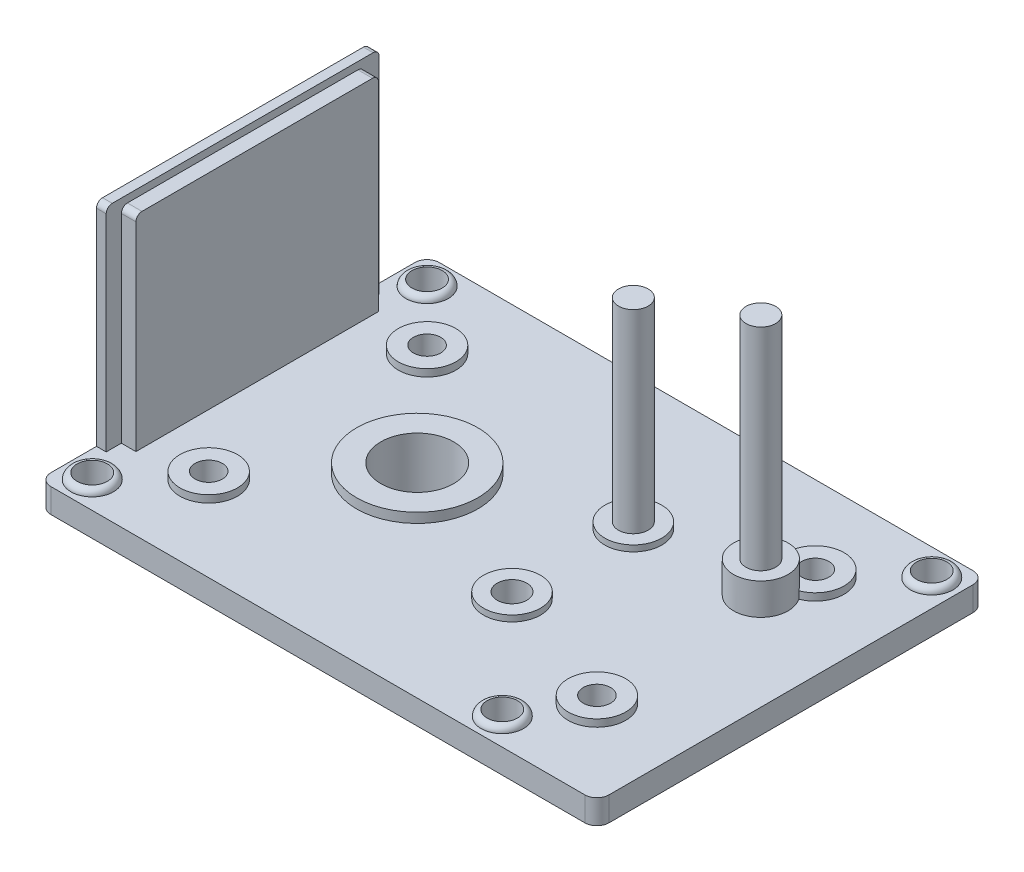
SolidWorks part; units mm, degrees
ref_plane "Front Plane" through (0, 0, 0) normal (0, 0, 1) x (1, 0, 0)
ref_plane "Top Plane" through (0, 0, 0) normal (0, 1, 0) x (1, 0, 0)
ref_plane "Right Plane" through (0, 0, 0) normal (1, 0, 0) x (0, 0, -1)
sketch "Sketch1" plane through (0, 0, 0) normal (0, 1, 0) x (1, 0, 0)
  line L0 (0, -55) -> (0, 55) construction
  line L1 (-23, 16) -> (23, 16)
  line L2 (-23, 16) -> (-23, -16)
  line L3 (-23, -16) -> (23, -16)
  line L4 (23, 16) -> (23, -16)
  line L5 (-55, 0) -> (55, 0) construction
  dimension "D1" = 46
  dimension "D2" = 23
  dimension "D3" = 32
  dimension "D4" = 16
extrude "Boss-Extrude1" add sketch "Sketch1" along normal blind 2
sketch "Sketch2" plane through (0, 2, 0) normal (0, 1, 0) x (1, 0, 0)
  line L0 (-23, -11.25) -> (-23, 11.25)
  line L1 (-1.1, 0) -> (1.1, 0) construction
  line L2 (-23, 16) -> (-23, -16) construction
  line L3 (-23, 11.25) -> (-22.2, 11.25)
  line L4 (-22.2, 11.25) -> (-22.2, 10)
  line L5 (-22.2, 10) -> (-21, 10)
  line L6 (-21, 10) -> (-21, -10)
  line L7 (-23, -11.25) -> (-22.2, -11.25)
  line L8 (-22.2, -11.25) -> (-22.2, -10)
  line L9 (-22.2, -10) -> (-21, -10)
  point P9 (-22.6, -11.25)
  point P11 (-23, 0)
  point P14 (-21, 0)
  dimension "D1" = 22.5
  dimension "D2" = 20
  dimension "D3" = 0.8
  dimension "D4" = 2
extrude "Boss-Extrude2" add sketch "Sketch2" along normal blind 17.5
sketch "Sketch3" plane through (0, 19.5, 0) normal (0, 1, 0) x (1, 0, 0)
  line L1 (-21, 10) -> (-22.2, 10)
  line L2 (-21, 10) -> (-21, -10)
  line L3 (-21, -10) -> (-22.2, -10)
  line L4 (-22.2, 10) -> (-22.2, -10)
extrude "Cut-Extrude1" cut sketch "Sketch3" against normal blind 0.6
fillet "Fillet1" radius 0.5 4 edges at (-22.6, 19.5, 11.25) (-21.6, 18.9, 10) (-22.6, 19.5, -11.25) (-21.6, 18.9, -10)
fillet "Fillet2" radius 1 4 edges at (-23, 1, -16) (23, 1, -16) (23, 1, 16) (-23, 1, 16)
sketch "Sketch4" plane through (0, 2, 0) normal (0, 1, 0) x (1, 0, 0)
  line L0 (23, -15) -> (23, 15) construction
  line L2 (22, 16) -> (-22, 16) construction
  line L5 (-23, 15) -> (-23, 11.25) construction
  line L7 (-1.1, 0) -> (1.1, 0) construction
  circle A1 centre (16, 9) radius 2.375
  circle A8 centre (-16, 9) radius 2.375
  circle A9 centre (16, -9) radius 2.375
  circle A10 centre (-16, -9) radius 2.375
  dimension "D1" = 7
  dimension "D3" = 4.75
  dimension "D4" = 4.75
  dimension "D2" = 7
  dimension "D5" = 7
  dimension "D6" = 7
extrude "Boss-Extrude3" add sketch "Sketch4" along normal blind 0.6
sketch "Sketch6" plane through (0, 2, 0) normal (0, 1, 0) x (1, 0, 0)
  line L0 (-1.1, 0) -> (1.1, 0) construction
  circle A3 centre (-16, 9) radius 1
  circle A7 centre (-16, 9) radius 2.375 construction
  circle A11 centre (-16, 9) radius 2.375 construction
  circle A12 centre (16, 9) radius 2.375
  circle A13 centre (16, 9) radius 2.375 construction
  circle A14 centre (16, 9) radius 1
  circle A15 centre (16, -9) radius 1
  circle A16 centre (-16, -9) radius 1
  dimension "D1" = 0
  dimension "D3" = 2
  dimension "D2" = 2
extrude "Boss-Extrude4" add sketch "Sketch6" along normal blind 0.75
hole_wizard "CSK for M6 Hex Socket Countersunk Cap Screw1" positions "Sketch11" profile "Sketch12" countersink size "M6" standard "ISO" end condition through all
sketch "Sketch11" plane through (0, 0, 0) normal (0, -1, 0) x (-1, 0, 0)
  line L0 (-22, 16) -> (22, 16) construction
  line L1 (-23, -15) -> (-23, 15) construction
  line L2 (23, 15) -> (23, -15) construction
  line L3 (22, -16) -> (-22, -16) construction
  point P0 (-20.8, 13.8)
  point P2 (20.8, 13.8)
  point P4 (20.8, -13.8)
  point P6 (-13, -13.8)
  dimension "D1" = 2.2
  dimension "D2" = 2.2
  dimension "D3" = 2.2
  dimension "D4" = 2.2
  dimension "2.2" = 2.2
  dimension "D5" = 2.2
  dimension "D6" = 2.2
  dimension "D7" = 10
sketch "Sketch12" plane through (20.8, 0, -13.8) normal (1, 0, 0) x (0, 0, -1)
  line L0 (0, 0) -> (0, 19.5)
  line L1 (0, 19.5) -> (1.25, 19.5)
  line L2 (1.25, 19.5) -> (1.25, 0.75)
  line L3 (1.25, 0.75) -> (2, 0)
  line L5 (2, 0) -> (0, 0)
  line L6 (-1.25, 0.75) -> (-2, 0) construction
  line L11 (0, -6.35) -> (0, 107.95) construction
  dimension "Thru Hole Dia." = 2.5
  dimension "Thru Hole Depth" = 19.5
  dimension "Near C'Sink Dia." = 4
  dimension "Near C'Sink Angle" = 90
sketch "Sketch13" plane through (0, 2, 0) normal (0, 1, 0) x (1, 0, 0)
  circle A0 centre (-20.8, 13.8) radius 1.25 construction
  circle A1 centre (-20.8, 13.8) radius 1.25
  circle A3 centre (13, -13.8) radius 1.25 construction
  circle A4 centre (-20.8, -13.8) radius 1.25 construction
  circle A6 centre (13, -13.8) radius 1.25
  circle A7 centre (-20.8, -13.8) radius 1.25
  circle A8 centre (-20.8, 13.8) radius 1.75
  circle A9 centre (-20.8, -13.8) radius 1.75
  circle A10 centre (13, -13.8) radius 1.75
  circle A12 centre (20.8, 13.8) radius 1.25 construction
  circle A13 centre (20.8, 13.8) radius 1.25
  circle A14 centre (20.8, 13.8) radius 1.75
  dimension "D1" = 0.5
extrude "Boss-Extrude5" add sketch "Sketch13" along normal blind 0.5
fillet "Fillet3" radius 0.5 4 edges at (-20.8, 2.5, 15.55) (13, 2.5, 15.55) (-20.8, 2.5, -12.05) (20.8, 2.5, -12.05)
sketch "Sketch14" plane through (0, 2, 0) normal (0, 1, 0) x (1, 0, 0)
  line L0 (-10.725, 0) -> (10.725, 0) construction
  line L1 (-23, -11.25) -> (-23, -15) construction
  circle A0 centre (-7.81, 0) radius 3
  circle A1 centre (-7.81, 0) radius 5
  dimension "D1" = 6
  dimension "D2" = 10
  dimension "D3" = 15.19
extrude "Boss-Extrude6" add sketch "Sketch14" along normal blind 0.8
sketch "Sketch15" plane through (0, 2, 0) normal (0, 1, 0) x (1, 0, 0)
  circle A1 centre (-7.81, 0) radius 3
  circle A2 centre (-7.81, 0) radius 3
  dimension "D1" = 0
extrude "Cut-Extrude2" cut sketch "Sketch15" against normal through all
sketch "Sketch16" plane through (0, 0, 0) normal (0, -1, 0) x (1, 0, 0)
  circle A3 centre (-7.81, 0) radius 3 construction
  circle A4 centre (-7.81, 0) radius 3
  circle A5 centre (-7.81, 0) radius 6.625
  dimension "D1" = 13.25
extrude "Boss-Extrude7" add sketch "Sketch16" along normal blind 1.6
sketch "Sketch18" plane through (0, 0, 0) normal (0, -1, 0) x (1, 0, 0)
  line L0 (10.725, 0) -> (-10.725, 0) construction
  circle A9 centre (-16, 9) radius 2.375 construction
  circle A10 centre (-16, 9) radius 2.375 construction
  circle A11 centre (16, 9) radius 2.375 construction
  circle A12 centre (16, 9) radius 2.375 construction
  circle A13 centre (-16, 9) radius 3.75
  circle A15 centre (16, 9) radius 3.75
  circle A16 centre (16, -9) radius 3.75
  circle A17 centre (-16, -9) radius 3.75
  dimension "D1" = 7.5
  dimension "D2" = 7.5
extrude "Boss-Extrude9" add sketch "Sketch18" along normal blind 2
sketch "Sketch20" plane through (0, 2, 0) normal (0, 1, 0) x (1, 0, 0)
  line L1 (-10.725, 0) -> (10.725, 0) construction
  line L2 (23, -15) -> (23, 15) construction
  circle A0 centre (5, 5) radius 1.225
  circle A1 centre (5, 5) radius 2.35
  circle A2 centre (5, -5) radius 2.35
  circle A3 centre (5, -5) radius 1.225
  dimension "D1" = 10
  dimension "D2" = 4.7
  dimension "D3" = 2.45
  dimension "D4" = 18
extrude "Boss-Extrude10" add sketch "Sketch20" along normal blind 0.5
sketch "Sketch21" plane through (0, 0, 0) normal (0, -1, 0) x (1, 0, 0)
  line L0 (5, 5) -> (5, -5) construction
  line L1 (8, 5) -> (8, -5)
  line L2 (2, 5) -> (2, -5)
  arc A0 (8, 5) -> (2, 5) centre (5, 5) ccw
  arc A1 (2, -5) -> (8, -5) centre (5, -5) ccw
  point P4 (5, 0)
  dimension "D1" = 6
extrude "Boss-Extrude11" add sketch "Sketch21" along normal blind 3
sketch "Sketch22" plane through (0, 2, 0) normal (0, 1, 0) x (1, 0, 0)
  circle A0 centre (5, 5) radius 1.225 construction
  circle A1 centre (5, 5) radius 1.225
  circle A2 centre (5, -5) radius 1.225 construction
  circle A3 centre (5, -5) radius 1.225
sketch "Sketch23" plane through (0, 2.5, 0) normal (0, 1, 0) x (1, 0, 0)
  circle A0 centre (5, 5) radius 1.225 construction
  circle A1 centre (5, 5) radius 1.225
  circle A2 centre (5, -5) radius 1.225 construction
  circle A3 centre (5, -5) radius 1.225
extrude "Cut-Extrude5" cut sketch "Sketch23" against normal blind 3
sketch "Sketch24" plane through (0, 2, 0) normal (0, 1, 0) x (1, 0, 0)
  line L2 (23, -15) -> (23, 15) construction
  line L3 (22, 16) -> (-22, 16) construction
  circle A0 centre (15, 5.51) radius 1.225
  circle A2 centre (15, 5.51) radius 2.25
  dimension "D1" = 8
  dimension "D3" = 4.5
  dimension "D4" = 2.45
  dimension "D2" = 10.49
extrude "Boss-Extrude12" add sketch "Sketch24" along normal blind 2.6
sketch "Sketch25" plane through (0, -0.5, 0) normal (0, 1, 0) x (1, 0, 0)
  circle A1 centre (5, 5) radius 1.225
  circle A2 centre (5, 5) radius 1.225
  circle A8 centre (15, 5.51) radius 1.225 construction
  circle A9 centre (15, 5.51) radius 1.225
  dimension "D1" = 0
extrude "Boss-Extrude13" add sketch "Sketch25" along normal blind 19 contours A2
sketch "Sketch27" plane through (0, 2, 0) normal (0, 1, 0) x (1, 0, 0)
  circle A0 centre (15, 5.51) radius 1.225 construction
  circle A1 centre (15, 5.51) radius 1.225
extrude "Boss-Extrude15" add sketch "Sketch27" along normal blind 20
sketch "Sketch29" plane through (0, -2, 0) normal (0, -1, 0) x (1, 0, 0)
  line L0 (13.75, 0) -> (-13.75, 0) construction
  circle A0 centre (16, 9) radius 1 construction
  circle A1 centre (-16, 9) radius 1 construction
  circle A2 centre (16, 9) radius 1 construction
  circle A3 centre (-16, 9) radius 1 construction
  circle A4 centre (-16, 9) radius 1.125
  circle A5 centre (16, 9) radius 1.125
  circle A6 centre (16, -9) radius 1.125
  circle A7 centre (-16, -9) radius 1.125
  dimension "D1" = 2.25
  dimension "D2" = 2.25
extrude "Cut-Extrude6" cut sketch "Sketch29" against normal through all
